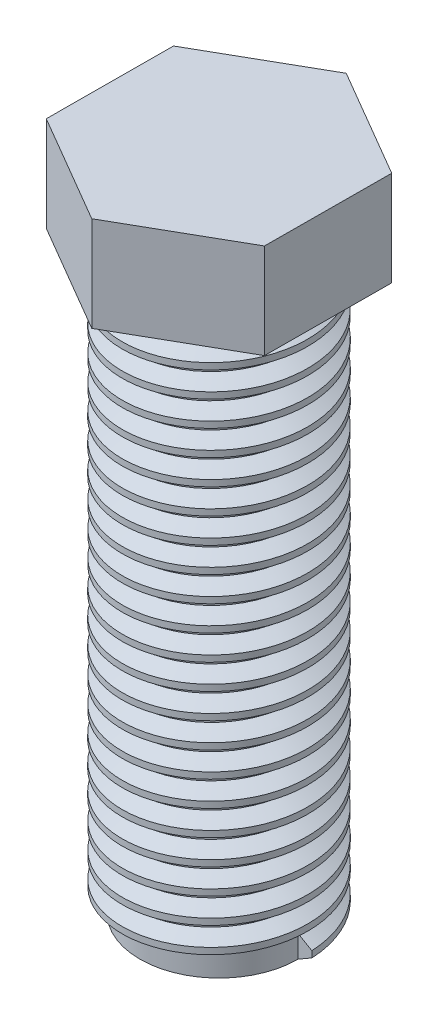
SolidWorks part; units mm, degrees
ref_plane "Front Plane" through (0, 0, 0) normal (0, 0, 1) x (1, 0, 0)
ref_plane "Top Plane" through (0, 0, 0) normal (0, 1, 0) x (1, 0, 0)
ref_plane "Right Plane" through (0, 0, 0) normal (1, 0, 0) x (0, 0, -1)
sketch "Sketch1" plane through (0, 0, 0) normal (0, 1, 0) x (1, 0, 0)
  circle A0 centre (0, 0) radius 12.5
  dimension "D1" = 25
extrude "Boss-Extrude1" add sketch "Sketch1" along normal blind 90
sketch "Sketch2" plane through (0, 90, 0) normal (0, 1, 0) x (1, 0, 0)
  line L1 (17.2709, -10.0854) -> (17.3697, 9.9144)
  line L2 (17.3697, 9.9144) -> (0.0987, 19.9998)
  line L3 (0.0987, 19.9998) -> (-17.2709, 10.0854)
  line L4 (-17.2709, 10.0854) -> (-17.3697, -9.9144)
  line L5 (-17.3697, -9.9144) -> (-0.0987, -19.9998)
  line L6 (-0.0987, -19.9998) -> (17.2709, -10.0854)
  circle A0 centre (0, 0) radius 17.3205 construction
  dimension "D1" = 20
extrude "Boss-Extrude2" add sketch "Sketch2" along normal blind 15
thread "Thread1" pitch 4 method extrude profile "Thread Profile1" start angle 0, offset 0, length 0, pitch 4, diameter 25
ref_plane "Plane1" through (12.5, 0, 0) normal (0, 0, -1) x (-1, 0, 0)
sketch "Thread Profile1" plane through (12.5, 0, 0) normal (0, 0, -1) x (-1, 0, 0)
  line L0 (0, 0) -> (0, 4) construction
  line L11 (0, 0) -> (0, 3.5)
  line L12 (0, 3.5) -> (-2.1651, 2.25)
  line L13 (-2.1651, 2.25) -> (-2.1651, 1.25)
  line L15 (-2.1651, 1.25) -> (0, 0)
  line L17 (-2.1651, 1.75) -> (0, 1.75) construction
  point P2 (0, 0)
  dimension "Pitch" = 4
  dimension "Profile_Angle" = 60
  dimension "Profile_Land" = 1
  dimension "Profile_Height" = 2.1651
